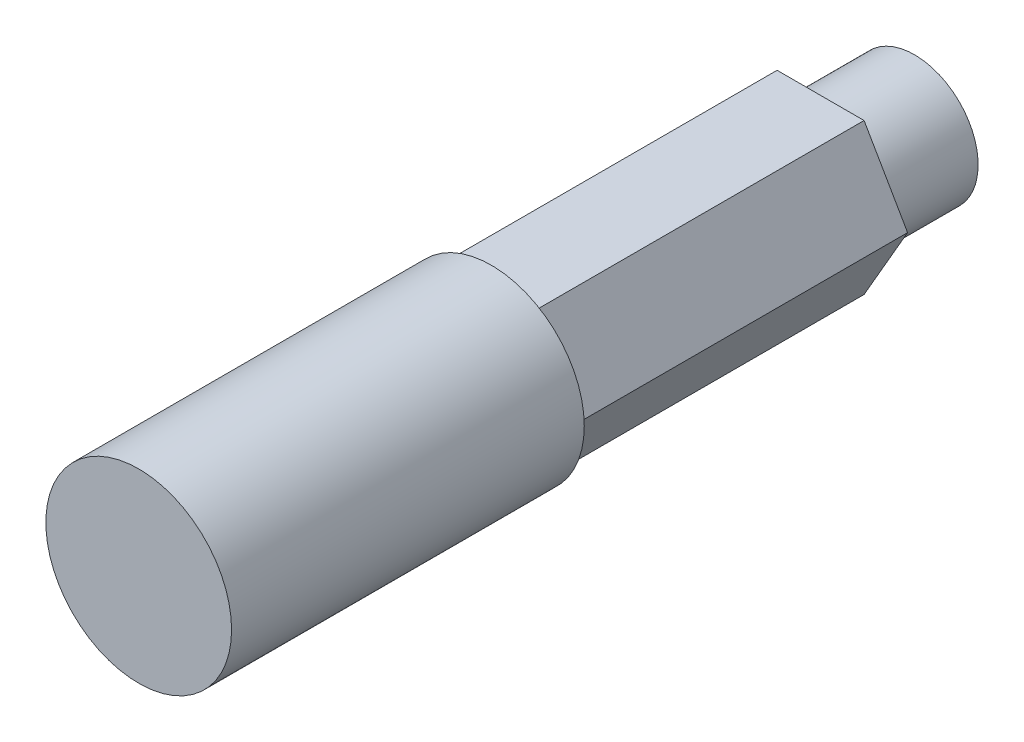
SolidWorks part; units mm, degrees
ref_plane "Front Plane" through (0, 0, 0) normal (0, 0, 1) x (1, 0, 0)
ref_plane "Top Plane" through (0, 0, 0) normal (0, 1, 0) x (1, 0, 0)
ref_plane "Right Plane" through (0, 0, 0) normal (1, 0, 0) x (0, 0, -1)
sketch "Sketch1" plane through (0, 0, 0) normal (0, 0, 1) x (1, 0, 0)
  line L1 (3.7, 0) -> (1.85, 3.2043)
  line L2 (1.85, 3.2043) -> (-1.85, 3.2043)
  line L3 (-1.85, 3.2043) -> (-3.7, 0)
  line L4 (-3.7, 0) -> (-1.85, -3.2043)
  line L5 (-1.85, -3.2043) -> (1.85, -3.2043)
  line L6 (1.85, -3.2043) -> (3.7, 0)
  circle A0 centre (0, 0) radius 3.7 construction
  circle A1 centre (0, 0) radius 3.2043 construction
  point P3 (0, 0)
  point P11 (3.7, 0)
  dimension "D1" = 7.4
extrude "Boss-Extrude1" add sketch "Sketch1" along normal blind 14
sketch "Sketch2" plane through (0, 0, 14) normal (0, 0, 1) x (1, 0, 0)
  circle A0 centre (0, 0) radius 3.95
  dimension "D1" = 7.9
extrude "Boss-Extrude2" add sketch "Sketch2" along normal blind 15
sketch "Sketch3" plane through (0, 0, 0) normal (0, 0, -1) x (-1, 0, 0)
  circle A0 centre (0, 0) radius 2.7
  dimension "D1" = 5.4
extrude "Boss-Extrude3" add sketch "Sketch3" along normal blind 4
